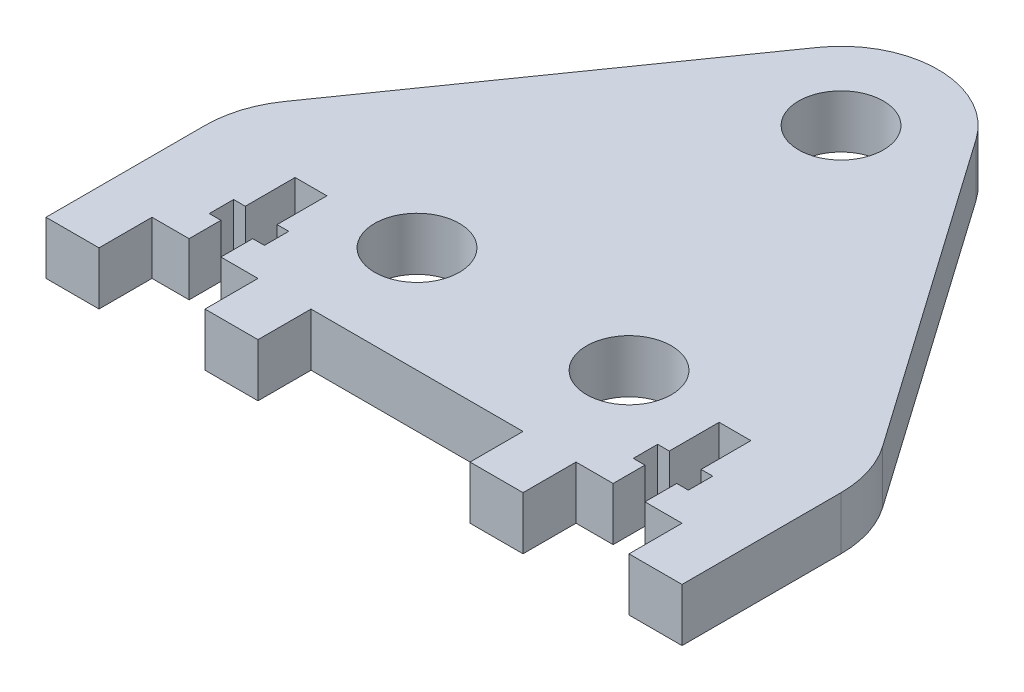
SolidWorks part; units mm, degrees
ref_plane "Front Plane" through (0, 0, 0) normal (0, 0, 1) x (1, 0, 0)
ref_plane "Top Plane" through (0, 0, 0) normal (0, 1, 0) x (1, 0, 0)
ref_plane "Right Plane" through (0, 0, 0) normal (1, 0, 0) x (0, 0, -1)
sketch "Sketch1" plane through (0, 0, 0) normal (0, 1, 0) x (1, 0, 0)
  line L1 (-30, 10) -> (-30, -5)
  line L2 (-30, -5) -> (-25, -5)
  line L3 (-10, -5) -> (-10, 0)
  line L4 (-10, 0) -> (10, 0)
  line L5 (10, -5) -> (10, 0)
  line L6 (30, -5) -> (25, -5)
  line L7 (30, 10) -> (30, -5)
  line L11 (0, 0) -> (0, 43.6328) construction
  line L13 (-28.1874, 15.7417) -> (-7.4911, 45.2534)
  line L14 (7.4911, 45.2534) -> (28.1874, 15.7417)
  line L36 (-25, -5) -> (-25, 0)
  line L37 (-25, 0) -> (-21.5, 0)
  line L38 (-21.5, 0) -> (-21.5, 3)
  line L39 (-21.5, 3) -> (-22.6, 3)
  line L40 (-22.6, 3) -> (-22.6, 5.3)
  line L41 (-22.6, 5.3) -> (-21.5, 5.3)
  line L42 (-21.5, 5.3) -> (-21.5, 10)
  line L43 (-21.5, 10) -> (-18.5, 10)
  line L44 (-18.5, 10) -> (-18.5, 5.3)
  line L45 (-18.5, 5.3) -> (-17.4, 5.3)
  line L46 (-17.4, 5.3) -> (-17.4, 3)
  line L47 (-17.4, 3) -> (-18.5, 3)
  line L48 (-18.5, 3) -> (-18.5, 0)
  line L49 (-18.5, 0) -> (-15, 0)
  line L50 (-15, 0) -> (-15, -5)
  line L51 (-15, -5) -> (-10, -5)
  line L52 (25, 0) -> (21.5, 0)
  line L53 (21.5, 0) -> (21.5, 3)
  line L54 (21.5, 3) -> (22.6, 3)
  line L55 (22.6, 5.3) -> (21.5, 5.3)
  line L56 (22.6, 3) -> (22.6, 5.3)
  line L57 (21.5, 5.3) -> (21.5, 10)
  line L58 (21.5, 10) -> (18.5, 10)
  line L59 (18.5, 10) -> (18.5, 5.3)
  line L60 (18.5, 5.3) -> (17.4, 5.3)
  line L61 (17.4, 5.3) -> (17.4, 3)
  line L62 (17.4, 3) -> (18.5, 3)
  line L63 (18.5, 3) -> (18.5, 0)
  line L64 (18.5, 0) -> (15, 0)
  line L65 (15, 0) -> (15, -5)
  line L66 (25, -5) -> (25, 0)
  line L67 (15, -5) -> (10, -5)
  arc A0 (-7.4911, 45.2534) -> (7.4911, 45.2534) centre (0, 40) cw
  circle A2 centre (0, 40) radius 4
  arc A3 (30, 10) -> (28.1874, 15.7417) centre (20, 10) ccw
  arc A4 (-30, 10) -> (-28.1874, 15.7417) centre (-20, 10) cw
  circle A5 centre (-10, 10) radius 4
  circle A6 centre (10, 10) radius 4
  point P68 (-16.75, 0)
  point P72 (-17.95, 3)
  point P73 (-22.05, 5.3)
  point P74 (-22.05, 3)
  point P78 (22.05, 3)
  point P80 (22.05, 5.3)
  point P88 (17.95, 3)
  point P91 (16.75, 0)
  dimension "D1" = 4
  dimension "D4" = 10
  dimension "D6" = 60
  dimension "D2" = 5
  dimension "D3" = 40
  dimension "D5" = 10
  dimension "D7" = 10
  dimension "D12" = 5
  dimension "D13" = 5
  dimension "D15" = 2.3
  dimension "D16" = 3
  dimension "D17" = 10
  dimension "D18" = 3
  dimension "D19" = 3.5
  dimension "D20" = 5.2
  dimension "D21" = 2.6
  dimension "D22" = 10
  dimension "D23" = 10
extrude "Boss-Extrude1" add sketch "Sketch1" along normal blind 5
